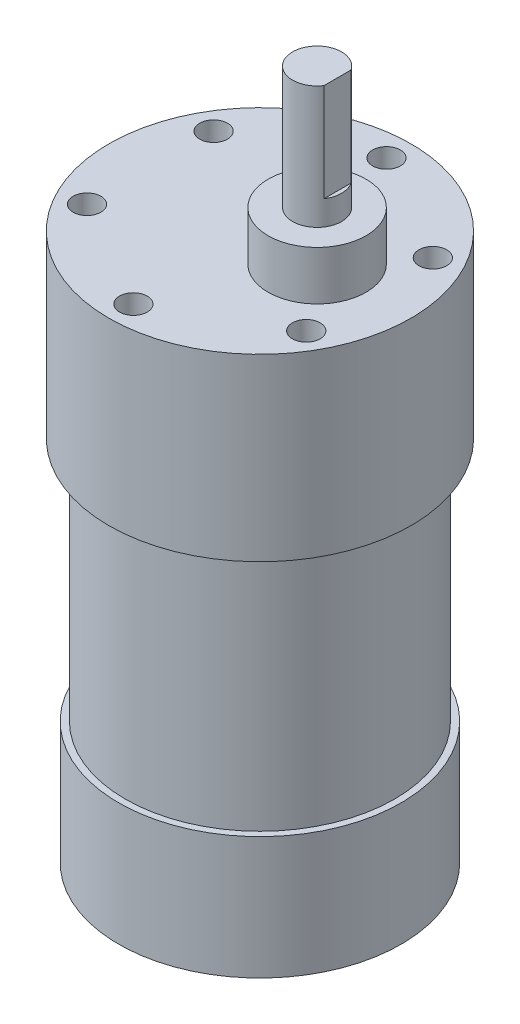
SolidWorks part; units mm, degrees
ref_plane "Front Plane" through (0, 0, 0) normal (0, 0, 1) x (1, 0, 0)
ref_plane "Top Plane" through (0, 0, 0) normal (0, 1, 0) x (1, 0, 0)
ref_plane "Right Plane" through (0, 0, 0) normal (1, 0, 0) x (0, 0, -1)
sketch "Sketch1" plane through (0, 0, 0) normal (0, 1, 0) x (1, 0, 0)
  circle A0 centre (0, 0) radius 16.5
extrude "Boss-Extrude1" add sketch "Sketch1" along normal blind 30
sketch "Sketch2" plane through (0, 0, 0) normal (0, -1, 0) x (1, 0, 0)
  circle A0 centre (0, 0) radius 2
extrude "Boss-Extrude2" add sketch "Sketch2" along normal blind 2
sketch "Sketch3" plane through (0, 30, 0) normal (0, 1, 0) x (1, 0, 0)
  circle A0 centre (0, 0) radius 18.5
extrude "Boss-Extrude3" add sketch "Sketch3" along normal blind 22
sketch "Sketch5" plane through (0, 52, 0) normal (0, 1, 0) x (1, 0, 0)
  line L0 (0, 0) -> (18.5, 0) construction
  line L1 (0, 0) -> (7, 0) construction
  circle A0 centre (0, 0) radius 18.5 construction
  circle A1 centre (7, 0) radius 6
extrude "Boss-Extrude4" add sketch "Sketch5" along normal blind 6
sketch "Sketch6" plane through (0, 58, 0) normal (0, 1, 0) x (1, 0, 0)
  circle A0 centre (7, 0) radius 3
extrude "Boss-Extrude5" add sketch "Sketch6" along normal blind 15
sketch "Sketch9" plane through (0, 73, 0) normal (0, 1, 0) x (1, 0, 0)
  line L0 (10, 0) -> (9.5, 0) construction
  line L1 (9.5, -1.6583) -> (9.5, 1.6583)
  circle A0 centre (7, 0) radius 3 construction
  arc A1 (9.5, 1.6583) -> (9.5, -1.6583) centre (7, 0) cw
  circle M2 centre (7, 0) radius 3
extrude "Cut-Extrude1" cut sketch "Sketch9" against normal blind 12 contours L0 A1 L1 | L0 L1 M2 region at (9.7015, 73, 0.6294) region at (9.7015, 73, -0.6294)
sketch "Sketch10" plane through (0, 52, 0) normal (0, 1, 0) x (1, 0, 0)
  line L0 (15.5, 0) -> (-15.5, 0) construction
  line L1 (0, -15.5) -> (0, 15.5) construction
  line L2 (0, 0) -> (-13.4234, 7.75) construction
  line L3 (13.4234, 7.75) -> (0, 7.75) construction
  circle A0 centre (0, 0) radius 15.5 construction
  circle A1 centre (0, -15.5) radius 1 construction
  circle A2 centre (0, 15.5) radius 1 construction
  circle A3 centre (-13.4234, 7.75) radius 1 construction
  circle A4 centre (-13.4234, -7.75) radius 1 construction
  circle A5 centre (13.4234, 7.75) radius 1 construction
  circle A6 centre (13.4234, -7.75) radius 1 construction
hole_wizard "M3 Clearance Hole1" positions "Sketch14" profile "Sketch15" hole size "M3" standard "IS"
sketch "Sketch14" plane through (0, 52, 0) normal (0, 1, 0) x (1, 0, 0)
  point P0 (0, -15.5)
  point P8 (-13.4234, -7.75)
  point P12 (0, 15.5)
  point P16 (-13.4234, 7.75)
  point P20 (13.4234, -7.75)
  point P24 (13.4234, 7.75)
sketch "Sketch15" plane through (0, 52, 15.5) normal (1, 0, 0) x (0, 0, 1)
  line L0 (0, 0) -> (0, 11.0215)
  line L1 (0, 11.0215) -> (1.7, 10)
  line L2 (1.7, 10) -> (1.7, 0)
  line L5 (1.7, 0) -> (0, 0)
  line L10 (0, 11.0215) -> (-1.7, 10) construction
  line L11 (0, -6.35) -> (0, 107.95) construction
  dimension "Hole Dia." = 3.4
  dimension "Hole Depth" = 10
  dimension "Drill Angle" = 118
sketch "Sketch16" plane through (0, 0, 0) normal (0, -1, 0) x (1, 0, 0)
  circle A0 centre (0, 0) radius 17.3
extrude "Boss-Extrude6" add sketch "Sketch16" along normal blind 15
